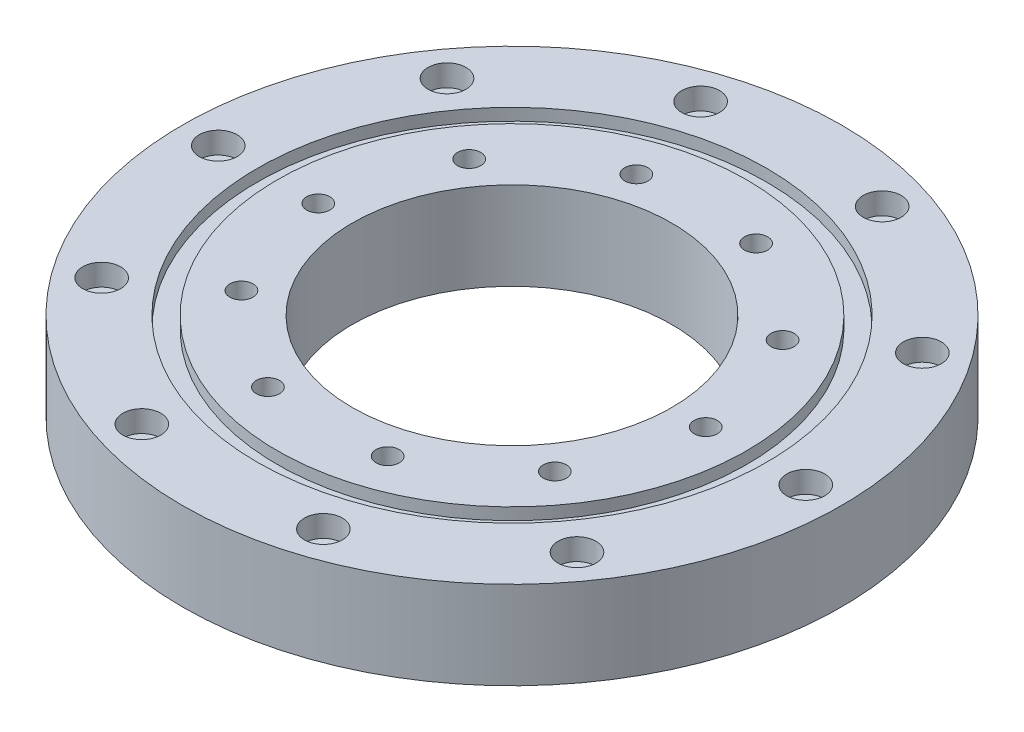
SolidWorks part; units mm, degrees
material "1.0037 (S235JR)"
ref_plane "Plan de face" through (0, 0, 0) normal (0, 0, 1) x (1, 0, 0)
ref_plane "Plan de dessus" through (0, 0, 0) normal (0, 1, 0) x (1, 0, 0)
ref_plane "Plan de droite" through (0, 0, 0) normal (1, 0, 0) x (0, 0, -1)
sketch "Esquisse1" plane through (0, 0, 0) normal (0, 1, 0) x (1, 0, 0)
  circle A0 centre (0, 0) radius 82.5
  circle A1 centre (0, 0) radius 40
  dimension "D1" = 165
  dimension "D2" = 80
extrude "Boss.-Extru.1" add sketch "Esquisse1" along normal blind 11 and the other way blind 11
sketch "Esquisse2" plane through (0, 11, 0) normal (0, 1, 0) x (1, 0, 0)
  line L0 (0, 0) -> (159.7855, 0) construction
  circle A0 centre (73.5417, 0) radius 2.75
  circle A1 centre (48.4945, 0) radius 2.75
  circle A2 centre (0, 0) radius 61.25 construction
  dimension "D1" = 122.5
  dimension "D2" = 5.5
  dimension "D3" = 5.5
extrude "Enlèv. mat.-Extru.1" cut sketch "Esquisse2" against normal through all both and the other way through all
sketch "Esquisse4" plane through (0, 11, 0) normal (0, 1, 0) x (1, 0, 0)
  circle A0 centre (73.5417, 0) radius 4.75
  dimension "D1" = 9.5
extrude "Enlèv. mat.-Extru.3" cut sketch "Esquisse4" against normal blind 5.4
sketch "Esquisse5" plane through (0, -11, 0) normal (0, -1, 0) x (1, 0, 0)
  circle A0 centre (48.4945, 0) radius 4.75
  dimension "D1" = 9.5
extrude "Enlèv. mat.-Extru.4" cut sketch "Esquisse5" against normal blind 5.4
pattern_circular "Répétition circulaire1" count 10 over 360 about axis through (0, 11, 0) along (0, 1, 0) of "Enlèv. mat.-Extru.1", "Enlèv. mat.-Extru.3", "Enlèv. mat.-Extru.4"
sketch "Esquisse3" plane through (0, 11, 0) normal (0, 1, 0) x (1, 0, 0)
  circle A0 centre (0, 0) radius 63.75
  circle A1 centre (0, 0) radius 58.75
  circle A2 centre (0, 0) radius 61.25 construction
  dimension "D1" = 122.5
  dimension "D2" = 127.5
  dimension "D3" = 117.5
extrude "Enlèv. mat.-Extru.2" cut sketch "Esquisse3" against normal blind 3 and the other way through all
mirror "Symétrie1" about plane through (0, 0, 0) normal (0, 1, 0) of "Enlèv. mat.-Extru.2"
hole_wizard "Dégagement M51" positions "Esquisse3D1" profile "Esquisse6" hole size "M5" standard "ISO"
sketch3d "Esquisse3D1"
  point P0 (48.4945, 648.6, 0)
  point P4 (39.2329, 654, 28.5044)
  point P8 (39.2329, 648.6, -28.5044)
  point P18 (-14.9856, 648.6, -46.121)
  point P22 (-39.2329, 648.6, -28.5044)
  point P34 (-14.9856, 648.6, 46.121)
  point P38 (14.9856, 648.6, 46.121)
  point P43 (-48.4945, 648.6, 0)
  point P47 (-39.2329, 648.6, 28.5044)
  point P58 (14.9856, 648.6, -46.121)
sketch "Esquisse6" plane through (-48.4945, -5.6, 0) normal (1, 0, 0) x (0, 0, -1)
  line L0 (0, 0) -> (0, 91.7425)
  line L1 (0, 91.7425) -> (2.9, 90)
  line L2 (2.9, 90) -> (2.9, 0)
  line L3 (2.9, 0) -> (0, 0)
  line L4 (0, 91.7425) -> (-2.9, 90) construction
  line L5 (0, -6.35) -> (0, 107.95) construction
  dimension "Diamètre du perçage" = 5.8
  dimension "Profondeur du perçage" = 90
  dimension "Angle de pointe" = 118
